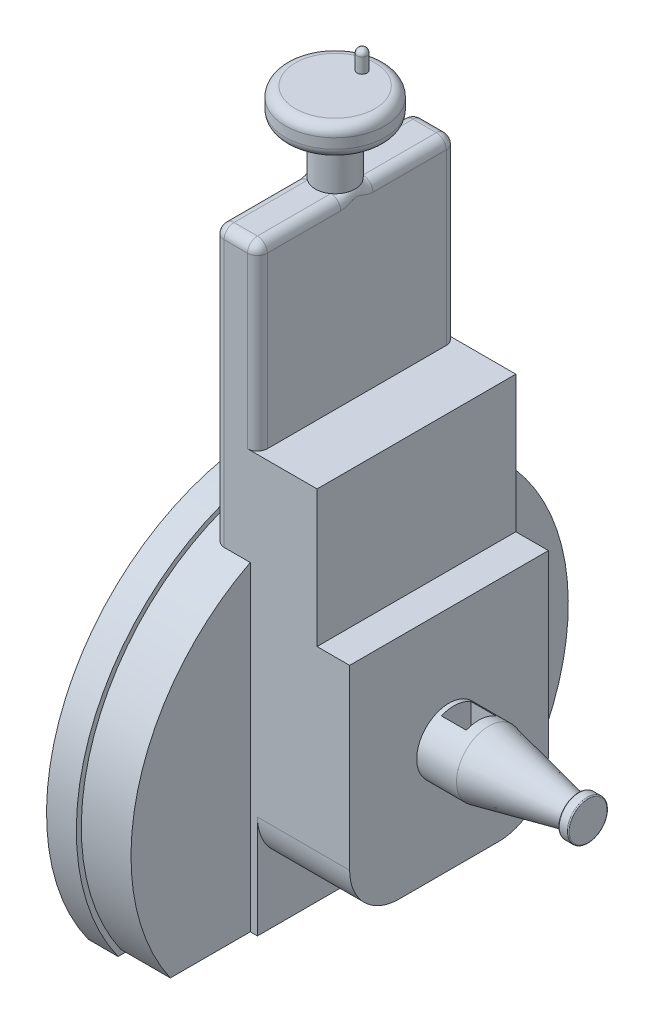
SolidWorks part; units mm, degrees
ref_plane "Front Plane" through (0, 0, 0) normal (0, 0, 1) x (1, 0, 0)
ref_plane "Top Plane" through (0, 0, 0) normal (0, 1, 0) x (1, 0, 0)
ref_plane "Right Plane" through (0, 0, 0) normal (1, 0, 0) x (0, 0, -1)
sketch "Sketch1" plane through (0, 0, 0) normal (1, 0, 0) x (0, 0, -1)
  circle A0 centre (-49.7878, 4.5092) radius 22.5
extrude "Boss-Extrude1" add sketch "Sketch1" along normal blind 3
sketch "Sketch3" plane through (3, 0, 0) normal (1, 0, 0) x (0, 0, -1)
  line L0 (-68.0878, -8.5812) -> (-31.4878, -8.5812)
  circle A0 centre (-49.7878, 4.5092) radius 22.5 construction
extrude "Cut-Extrude1" cut sketch "Sketch3" against normal through all and the other way through all flip side to cut
sketch "Sketch4" plane through (3, 0, 0) normal (1, 0, 0) x (0, 0, -1)
  line L0 (-67.8289, -8.0812) -> (-31.7467, -8.0812)
  arc A0 (-31.7467, -8.0812) -> (-67.8289, -8.0812) centre (-49.7878, 4.5092) ccw
extrude "Boss-Extrude2" add sketch "Sketch4" along normal blind 2
sketch "Sketch5" plane through (5, 0, 0) normal (1, 0, 0) x (0, 0, -1)
  line L1 (-67.8289, -8.0812) -> (-31.7467, -8.0812)
  line L2 (-67.8289, -8.0812) -> (-31.7467, -8.0812)
  arc A1 (-31.7467, -8.0812) -> (-67.8289, -8.0812) centre (-49.7878, 4.5092) ccw
  arc A2 (-31.7467, -8.0812) -> (-67.8289, -8.0812) centre (-49.7878, 4.5092) ccw
  dimension "D1" = 0
extrude "Boss-Extrude3" add sketch "Sketch5" along normal blind 3
sketch "Sketch6" plane through (0, -8.0812, 0) normal (0, -1, 0) x (-1, 0, 0)
  line L0 (-8, -49.7878) -> (-8, -59.7878)
  line L1 (-8, -67.8289) -> (-8, -31.7467) construction
  line L2 (-8, -49.7878) -> (-8, -39.7878)
  line L4 (-8.7221, -39.7878) -> (-4.3645, -39.7878)
  line L5 (-8.7221, -39.7878) -> (-8.7221, -59.7878)
  line L6 (-8.7221, -59.7878) -> (-4.3645, -59.7878)
  line L7 (-4.3645, -39.7878) -> (-4.3645, -59.7878)
extrude "Boss-Extrude4" add sketch "Sketch6" against normal blind 60 contours L5 L6 L7 L4
sketch "Sketch8" plane through (8.7221, 0, 0) normal (1, 0, 0) x (0, 0, -1)
  line L0 (-59.7878, 51.9188) -> (-59.7878, -8.0812) construction
  line L1 (-59.7878, 33.8786) -> (-39.7878, 33.8786)
  line L2 (-59.7878, 33.8786) -> (-59.7878, -2.715)
  line L3 (-59.7878, -2.715) -> (-39.7878, -2.715)
  line L4 (-39.7878, 33.8786) -> (-39.7878, -2.715)
extrude "Boss-Extrude5" add sketch "Sketch8" along normal blind 6
sketch "Sketch10" plane through (8, 0, 0) normal (1, 0, 0) x (0, 0, -1)
  line L0 (-39.7878, 24.1052) -> (-39.7878, -8.0812) construction
  line L1 (-59.7878, -2.715) -> (-39.7878, -2.715)
  line L2 (-59.7878, -2.715) -> (-59.7878, 20.1431)
  line L3 (-59.7878, 20.1431) -> (-39.7878, 20.1431)
  line L4 (-39.7878, -2.715) -> (-39.7878, 20.1431)
extrude "Boss-Extrude6" add sketch "Sketch10" along normal blind 10
fillet "Fillet1" radius 5 1 edges
fillet "Fillet2" radius 5 1 edges
sketch "Sketch11" plane through (0, 51.9188, 0) normal (0, 1, 0) x (1, 0, 0)
  circle A0 centre (6.5433, -49.7878) radius 2
extrude "Boss-Extrude7" add sketch "Sketch11" along normal blind 5
sketch "Sketch12" plane through (0, 56.9188, 0) normal (0, 1, 0) x (1, 0, 0)
  circle A0 centre (6.5433, -49.7878) radius 5
extrude "Boss-Extrude8" add sketch "Sketch12" along normal blind 3
fillet "Fillet4" radius 1 1 edges at (6.5433, 56.9188, 54.7878)
fillet "Fillet5" radius 1 1 edges at (6.5433, 59.9188, 54.7878)
fillet "Fillet6" radius 1 1 edges at (4.3645, 38.012, 59.7878)
fillet "Fillet7" radius 1 1 edges at (4.3645, 38.012, 39.7878)
fillet "Fillet8" radius 1 5 edges at (7.0433, 51.9188, 39.7878) (4.6574, 51.9188, 40.0807) (4.3645, 51.9188, 49.7878) (4.6574, 51.9188, 59.4949) (7.0433, 51.9188, 59.7878)
fillet "Fillet9" radius 1 5 edges at (8.7221, 51.6259, 40.0807) (8.7221, 51.6259, 59.4949) (8.7221, 51.9188, 49.7878)
sketch "Sketch13" plane through (0, 59.9188, 0) normal (0, 1, 0) x (1, 0, 0)
  circle A0 centre (6.5433, -47.0747) radius 0.5
extrude "Boss-Extrude9" add sketch "Sketch13" along normal blind 2
fillet "Fillet11" radius 0.5 1 edges at (6.5433, 61.9188, 47.5747)
sketch "Sketch14" plane through (18, 0, 0) normal (1, 0, 0) x (0, 0, -1)
  circle A2 centre (-49.7878, 8.6012) radius 3.25
extrude "Boss-Extrude10" add sketch "Sketch14" along normal blind 4 separate body
sketch "Sketch15" plane through (22, 0, 0) normal (1, 0, 0) x (0, 0, -1)
  circle A0 centre (-49.7878, 8.6012) radius 3.25
extrude "Boss-Extrude11" add sketch "Sketch15" along normal blind 9 draft 12
sketch "Sketch16" plane through (31, 0, 0) normal (1, 0, 0) x (0, 0, -1)
  circle A0 centre (-49.7878, 8.6012) radius 2
extrude "Boss-Extrude12" add sketch "Sketch16" along normal blind 1
fillet "Fillet12" radius 0.1 1 edges at (31, 8.6012, 47.7878)
fillet "Fillet13" radius 0.1 1 edges at (32, 8.6012, 47.7878)
sketch "Sketch17" plane through (0, 59.9188, 0) normal (0, 1, 0) x (1, 0, 0)
  line L1 (18.4797, -51.0358) -> (20.9797, -51.0358)
  line L2 (18.4797, -51.0358) -> (18.4797, -48.0358)
  line L3 (18.4797, -48.0358) -> (20.9797, -48.0358)
  line L4 (20.9797, -51.0358) -> (20.9797, -48.0358)
  line L5 (18.4797, -51.0358) -> (20.9797, -48.0358) construction
  line L6 (18.4797, -48.0358) -> (20.9797, -51.0358) construction
  dimension "D1" = 2.5
  dimension "D2" = 3
extrude "Cut-Extrude2" cut sketch "Sketch17" against normal blind 60
